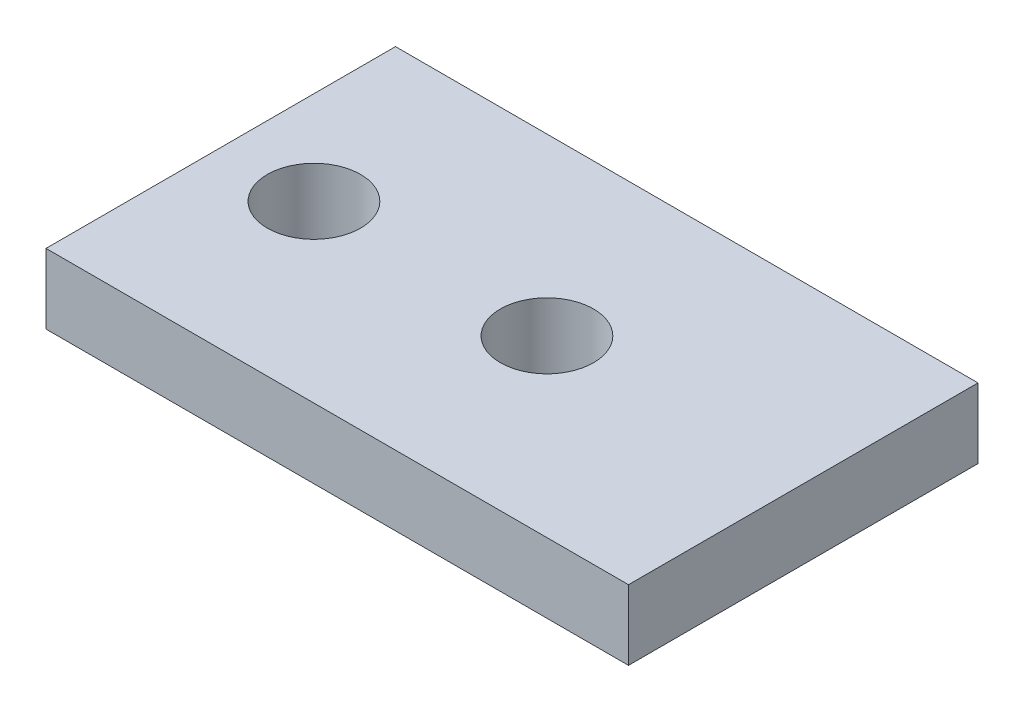
SolidWorks part; units mm, degrees
ref_plane "Спереди" through (0, 0, 0) normal (0, 0, 1) x (1, 0, 0)
ref_plane "Сверху" through (0, 0, 0) normal (0, 1, 0) x (1, 0, 0)
ref_plane "Справа" through (0, 0, 0) normal (1, 0, 0) x (0, 0, -1)
sketch "Эскиз2" plane through (0, 0, 0) normal (0, 1, 0) x (1, 0, 0)
  line L0 (-25, 15) -> (25, -15) construction
  line L1 (-25, 15) -> (25, 15)
  line L2 (-25, 15) -> (-25, -15)
  line L3 (-25, -15) -> (25, -15)
  line L4 (25, 15) -> (25, -15)
  line L5 (25, 0) -> (3, 0) construction
  circle A0 centre (3, 0) radius 4
  circle A1 centre (-17, 0) radius 4
  dimension "D3" = 8
  dimension "D5" = 20
  dimension "D1" = 50
  dimension "D2" = 30
  dimension "D4" = 8
extrude "Бобышка-Вытянуть1" add sketch "Эскиз2" along normal blind 6
ref_axis "Ось1" through (-17, 6, 0) along (0, -1, 0)
ref_plane "Плоскость1" through (-17, 0, 0) normal (1, 0, 0) x (0, 0, -1)
